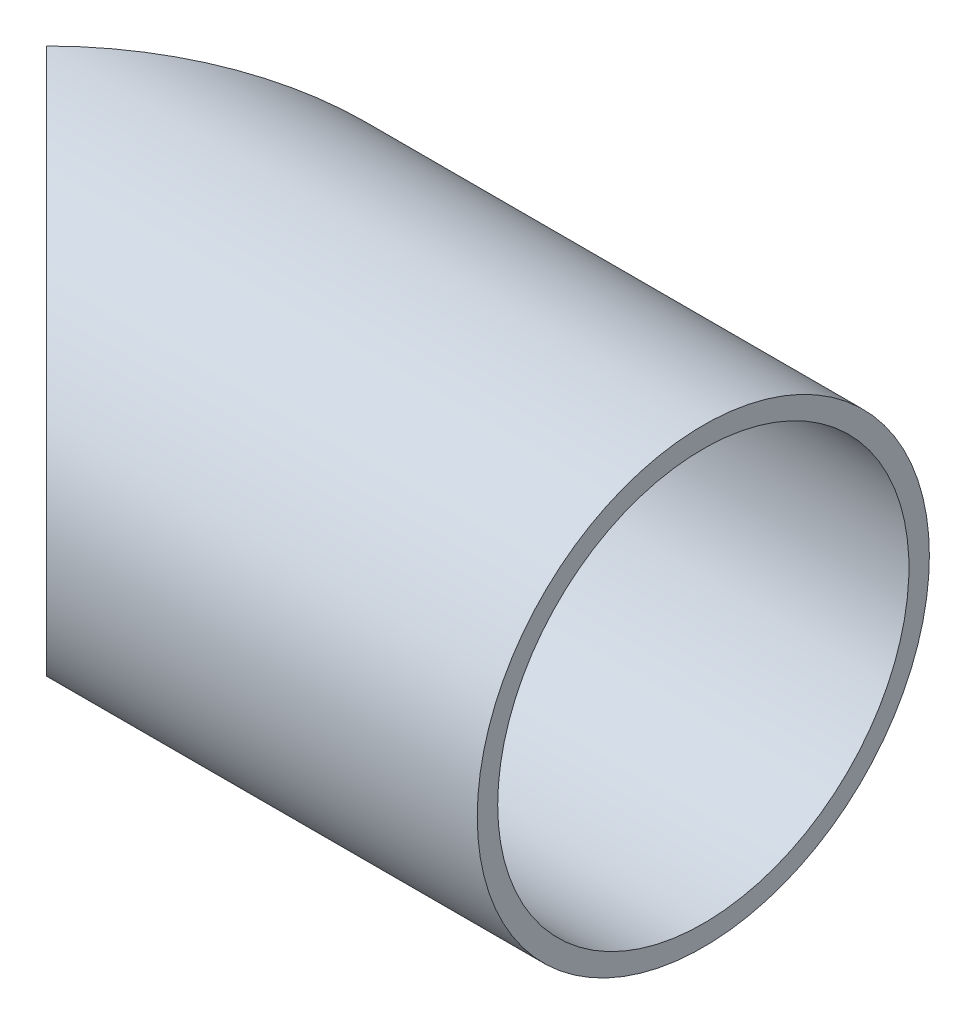
SolidWorks part; units mm, degrees
material "6061-T6 (SS)"
ref_plane "Front" through (0, 0, 0) normal (0, 0, 1) x (1, 0, 0)
ref_plane "Top" through (0, 0, 0) normal (0, 1, 0) x (1, 0, 0)
ref_plane "Right" through (0, 0, 0) normal (1, 0, 0) x (0, 0, -1)
sketch "Sketch1" plane through (0, 0, 0) normal (0, 0, 1) x (1, 0, 0)
  line L0 (0, 0) -> (0, 9.55) construction
  line L1 (0, 9.55) -> (20, 9.55)
  line L6 (0, 10.5) -> (0, 9.55)
  line L7 (0, 0) -> (20, 0) construction
  line L8 (0, 9.55) -> (-10.5, 9.55)
  line L9 (0, 10.5) -> (-10.5, 10.5)
  line L10 (-10.5, 10.5) -> (-10.5, 9.55)
  line L11 (-10.5, 10.5) -> (0, 10.5)
  line L12 (-10.5, -10.5) -> (-10.5, 10.5)
  line L14 (0, 9.55) -> (20, 9.55)
  line L15 (0, 9.55) -> (0, 10.5)
  line L16 (0, 10.5) -> (20, 10.5)
  line L17 (20, 9.55) -> (20, 10.5)
  arc A0 (-10.5, 10.5) -> (-10.5, -10.5) centre (-10.5, 0) cw
  point P18 (0, 0)
  dimension "D5" = 10.5
  dimension "D1" = 9.55
  dimension "D2" = 20
revolve "Revolve1" add sketch "Sketch1" angle 360 about L7 region at (10, 10.025, 0) region at (-3.8508, 10.0613, 0)
extrude "Cut-Extrude1" cut sketch "Sketch1<3>" against normal through all both and the other way through all contours A0 L8 L12 | A0 L10 L8 region at (-5.9977, -0.1626, 0) region at (-8.853, 9.9315, 0)
sketch "Sketch1<3>" plane through (0, 0, 0) normal (0, 0, 1) x (1, 0, 0) same geometry as "Sketch1"
sketch "Sketch2" plane through (0, 0, 0) normal (0, 0, 1) x (1, 0, 0)
  line L0 (0, 0) -> (2, 0) construction
  circle A0 centre (2, 0) radius 0.9
  dimension "D2" = 1.8
  dimension "D1" = 2
extrude "Cut-Extrude2" cut sketch "Sketch2" against normal through all
